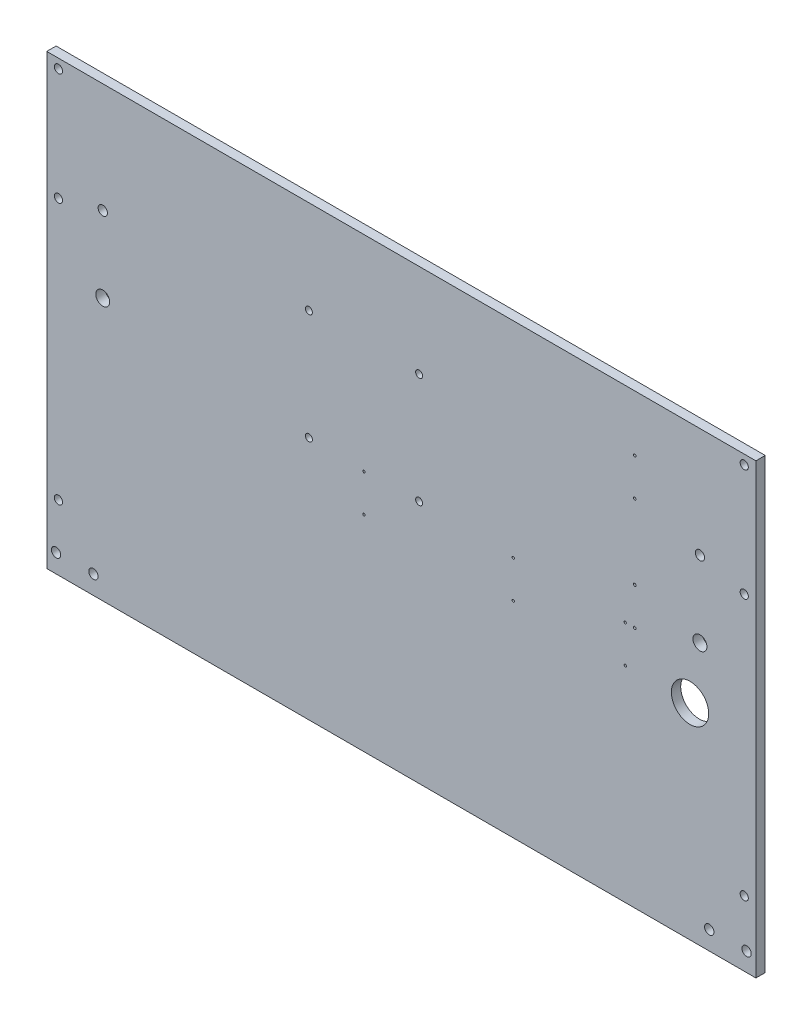
SolidWorks part; units mm, degrees
ref_plane "Front Plane" through (0, 0, 0) normal (0, 0, 1) x (1, 0, 0)
ref_plane "Top Plane" through (0, 0, 0) normal (0, 1, 0) x (1, 0, 0)
ref_plane "Right Plane" through (0, 0, 0) normal (1, 0, 0) x (0, 0, -1)
sketch "Sketch1" plane through (0, 0, 0) normal (0, 0, 1) x (1, 0, 0)
  line L1 (-241.3, -152.4) -> (241.3, -152.4)
  line L2 (-241.3, -152.4) -> (-241.3, 152.4)
  line L3 (-241.3, 152.4) -> (241.3, 152.4)
  line L4 (241.3, -152.4) -> (241.3, 152.4)
  line L5 (-241.3, -152.4) -> (241.3, 152.4) construction
  line L6 (-241.3, 152.4) -> (241.3, -152.4) construction
  point P0 (0, 0)
  dimension "D1" = 482.6
  dimension "D2" = 304.8
extrude "Boss-Extrude1" add sketch "Sketch1" along normal blind 6.35
sketch "Sketch2" plane through (0, 0, 6.35) normal (0, 0, 1) x (1, 0, 0)
  line L0 (-241.3, 0) -> (241.3, 0) construction
  line L1 (-241.3, 152.4) -> (-241.3, -152.4) construction
  line L2 (241.3, -152.4) -> (241.3, 152.4) construction
  line L3 (241.3, 152.4) -> (-241.3, 152.4) construction
  circle A0 centre (-233.3498, 146.05) radius 2.7813
  circle A1 centre (-233.3498, -107.95) radius 2.7813
  circle A2 centre (-233.3498, 69.85) radius 2.7813
  dimension "D2" = 5.5626
  dimension "D3" = 5.5626
  dimension "D6" = 5.5626
  dimension "D1" = 7.9502
  dimension "D4" = 6.35
  dimension "D5" = 254
  dimension "D7" = 76.2
extrude "Cut-Extrude1" cut sketch "Sketch2" against normal through all
mirror "Mirror1" about plane through (0, 0, 0) normal (1, 0, 0) of "Cut-Extrude1"
sketch "Sketch3" plane through (0, 0, 6.35) normal (0, 0, 1) x (1, 0, 0)
  line L0 (-241.3, -139.7) -> (241.3, -139.7) construction
  line L1 (-241.3, 152.4) -> (-241.3, -152.4) construction
  line L2 (241.3, -152.4) -> (241.3, 152.4) construction
  line L3 (-241.3, -152.4) -> (241.3, -152.4) construction
  circle A0 centre (-234.95, -139.7) radius 3.175
  circle A1 centre (-209.55, -139.7) radius 3.175
  dimension "D2" = 6.35
  dimension "D3" = 6.35
  dimension "D4" = 25.4
  dimension "D5" = 6.35
  dimension "D1" = 12.7
extrude "Cut-Extrude2" cut sketch "Sketch3" against normal through all
mirror "Mirror2" about plane through (0, 0, 0) normal (1, 0, 0) of "Cut-Extrude2"
sketch "Sketch4" plane through (0, 0, 6.35) normal (0, 0, 1) x (1, 0, 0)
  line L0 (241.3, 152.4) -> (-241.3, 152.4) construction
  circle A0 centre (196.469, -12.7) radius 12.7
  dimension "D2" = 25.4
  dimension "D1" = 196.469
  dimension "D3" = 165.1
extrude "Cut-Extrude3" cut sketch "Sketch4" against normal through all
sketch "Sketch5" plane through (0, 0, 6.35) normal (0, 0, 1) x (1, 0, 0)
  line L0 (241.3, 152.4) -> (-241.3, 152.4) construction
  line L1 (-62.9, 13.9) -> (12.1, 13.9) construction
  line L2 (-62.9, 13.9) -> (-62.9, 88.9) construction
  line L3 (-62.9, 88.9) -> (12.1, 88.9) construction
  line L4 (12.1, 13.9) -> (12.1, 88.9) construction
  line L5 (-62.9, 13.9) -> (12.1, 88.9) construction
  line L6 (-62.9, 88.9) -> (12.1, 13.9) construction
  circle A0 centre (-62.9, 88.9) radius 2.3749
  circle A1 centre (12.1, 88.9) radius 2.3749
  circle A2 centre (12.1, 13.9) radius 2.3749
  circle A3 centre (-62.9, 13.9) radius 2.3749
  point P0 (-25.4, 51.4)
  dimension "D4" = 4.7498
  dimension "D5" = 4.7498
  dimension "D6" = 4.7498
  dimension "D7" = 4.7498
  dimension "D1" = 75
  dimension "D2" = 75
  dimension "D3" = 63.5
  dimension "D8" = 25.4
extrude "Cut-Extrude4" cut sketch "Sketch5" against normal through all
sketch "Sketch6" plane through (0, 0, 6.35) normal (0, 0, 1) x (1, 0, 0)
  line L0 (241.3, -152.4) -> (241.3, 152.4) construction
  line L1 (-241.3, 152.4) -> (-241.3, -152.4) construction
  circle A0 centre (-203.2, 77.7271) radius 3.175
  circle A1 centre (-203.2, 26.0961) radius 4.7625
  circle A2 centre (203.2, 77.7271) radius 3.175
  circle A3 centre (203.2, 26.0961) radius 4.7625
  dimension "D1" = 6.35
  dimension "D2" = 6.35
  dimension "D3" = 9.525
  dimension "D4" = 9.525
  dimension "D5" = 38.1
  dimension "D6" = 38.1
extrude "Cut-Extrude5" cut sketch "Sketch6" against normal through all
sketch "Sketch7" plane through (0, 0, 6.35) normal (0, 0, 1) x (1, 0, 0)
  line L0 (158.8215, 152.4) -> (158.8215, -152.4) construction
  line L1 (241.3, 152.4) -> (-241.3, 152.4) construction
  line L2 (-241.3, -152.4) -> (241.3, -152.4) construction
  circle A0 centre (158.8215, 114.3) radius 0.889
  circle A1 centre (158.8215, 88.9) radius 0.889
  circle A2 centre (158.8215, 38.1) radius 0.889
  circle A3 centre (158.8215, 12.7) radius 0.889
  dimension "D1" = 1.778
  dimension "D2" = 1.778
  dimension "D3" = 1.778
  dimension "D4" = 1.778
  dimension "D8" = 38.1
  dimension "D5" = 25.4
  dimension "D6" = 25.4
  dimension "D7" = 50.8
extrude "Cut-Extrude6" cut sketch "Sketch7" against normal through all
sketch "Sketch8" plane through (0, 0, 6.35) normal (0, 0, 1) x (1, 0, 0)
  circle A0 centre (-25.4, 12.7) radius 0.8255
  circle A1 centre (-25.4, -12.7) radius 0.8255
  circle A2 centre (76.2, 12.7) radius 0.7937
  circle A3 centre (76.2, -12.7) radius 0.7937
  circle A4 centre (152.4, 12.7) radius 0.7937
  circle A5 centre (152.4, -12.7) radius 0.7937
  point P11 (0, 0)
  point P12 (0, 0)
  point P15 (0, 0)
  dimension "D1" = 1.651
  dimension "D2" = 1.651
  dimension "D7" = 1.5875
  dimension "D8" = 1.5875
  dimension "D9" = 1.5875
  dimension "D10" = 1.5875
  dimension "D3" = 25.4
  dimension "D4" = 12.7
  dimension "D5" = 25.4
  dimension "D6" = 101.6
  dimension "D11" = 76.2
extrude "Cut-Extrude7" cut sketch "Sketch8" against normal through all
